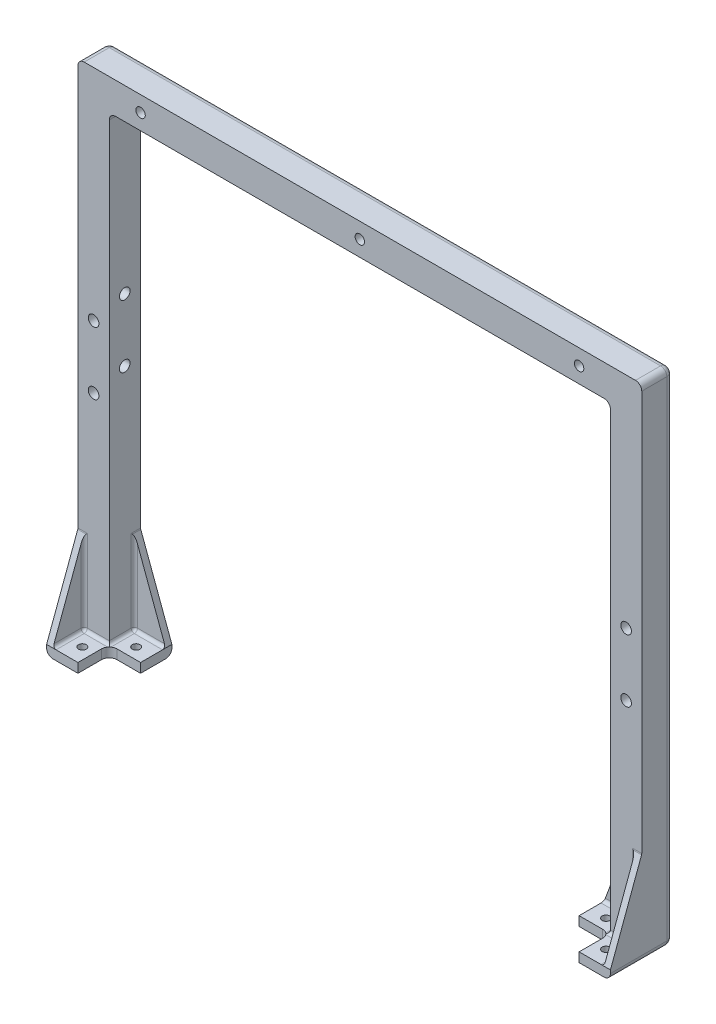
SolidWorks part; units mm, degrees
material "PLA"
ref_plane "Front Plane" through (0, 0, 0) normal (0, 0, 1) x (1, 0, 0)
ref_plane "Top Plane" through (0, 0, 0) normal (0, 1, 0) x (1, 0, 0)
ref_plane "Right Plane" through (0, 0, 0) normal (1, 0, 0) x (0, 0, -1)
sketch "Sketch1" plane through (0, 0, 0) normal (0, 0, 1) x (1, 0, 0)
  line L0 (0, 0) -> (39473.4142, 0) construction
  line L1 (0, 0) -> (0, 39473.4142) construction
  line L2 (-101.6, 0) -> (-101.6, 190.5)
  line L3 (-101.6, 190.5) -> (101.6, 190.5)
  line L4 (-101.6, 0) -> (-114.3, 0)
  line L5 (-114.3, 0) -> (-114.3, 203.2)
  line L6 (-114.3, 203.2) -> (114.3, 203.2)
  line L7 (114.3, 0) -> (114.3, 203.2)
  line L8 (101.6, 0) -> (114.3, 0)
  line L9 (101.6, 0) -> (101.6, 190.5)
  point P12 (0, 203.2)
  point P15 (0, 190.5)
  dimension "D1" = 190.5
  dimension "D2" = 203.2
  dimension "D3" = 203.2
  dimension "D4" = 228.6
extrude "Frame" add sketch "Sketch1" along normal blind 12.7
sketch "Sketch3" plane through (-114.3, 0, 0) normal (-1, 0, 0) x (0, 0, 1)
  line L0 (0, 0) -> (25.4, 0)
  line L1 (25.4, 0) -> (25.4, 3.81)
  line L2 (25.4, 3.81) -> (12.7, 38.1)
  line L3 (12.7, 38.1) -> (0, 38.1)
  line L4 (0, 203.2) -> (0, 0) construction
  line L5 (0, 38.1) -> (0, 0)
  line L6 (12.7, 203.2) -> (12.7, 0) construction
  dimension "D1" = 12.7
  dimension "D2" = 0
  dimension "D3" = 3.81
  dimension "D4" = 38.1
extrude "gusset_side" add sketch "Sketch3" against normal blind 2.54
mirror "gusset_mirror" about plane through (0, 0, 0) normal (1, 0, 0) of "gusset_side"
sketch "Sketch4" plane through (0, 0, 0) normal (0, -1, 0) x (-1, 0, 0)
  line L0 (101.6, 0) -> (101.6, -25.4)
  line L1 (101.6, -25.4) -> (114.3, -25.4)
  line L2 (114.3, -25.4) -> (114.3, 0) construction
  line L3 (114.3, -25.4) -> (114.3, 0)
  line L4 (114.3, 0) -> (101.6, 0)
  line L6 (111.76, -25.4) -> (114.3, -25.4) construction
extrude "bottom_mount_plate" add sketch "Sketch4" against normal up to vertex (3.81 mm away) up to point (-111.76, 3.81, 25.4)
mirror "Mirror2" about plane through (0, 0, 0) normal (1, 0, 0) of "bottom_mount_plate"
sketch "Sketch5" plane through (0, 0, 0) normal (0, 0, -1) x (-1, 0, 0)
  line L0 (-114.3, 0) -> (-88.9, 0)
  line L1 (-88.9, 0) -> (-88.9, 3.81)
  line L2 (-88.9, 3.81) -> (-101.6, 38.1)
  line L3 (-101.6, 38.1) -> (-114.3, 38.1)
  line L4 (-114.3, 0) -> (-114.3, 203.2) construction
  line L5 (-114.3, 38.1) -> (-114.3, 0)
  line L6 (-101.6, 190.5) -> (-101.6, 0) construction
  dimension "D1" = 3.81
  dimension "D2" = 0
  dimension "D3" = 38.1
  dimension "D4" = 12.7
extrude "gusset_front" add sketch "Sketch5" against normal blind 2.54
mirror "Mirror3" about plane through (0, 0, 0) normal (1, 0, 0) of "gusset_front"
sketch "Sketch6" plane through (0, 0, 0) normal (0, -1, 0) x (1, 0, 0)
  line L0 (114.3, 0) -> (88.9, 0)
  line L1 (88.9, 0) -> (88.9, 12.7)
  line L2 (88.9, 12.7) -> (114.3, 12.7)
  line L3 (114.3, 25.4) -> (114.3, 0) construction
  line L4 (114.3, 12.7) -> (114.3, 0)
  dimension "D1" = 12.7
extrude "bottom_mount_plate2" add sketch "Sketch6" against normal up to vertex (3.81 mm away) up to point (88.9, 3.81, 2.54)
mirror "Mirror4" about plane through (0, 0, 0) normal (1, 0, 0) of "bottom_mount_plate2"
fillet "Fillet1" radius 1.27 8 edges at (101.6, 38.1, 1.27) (-101.6, 20.955, 2.54) (-101.6, 38.1, 1.27) (101.6, 20.955, 2.54) (-113.03, 38.1, 12.7) (111.76, 20.955, 12.7) (113.03, 38.1, 12.7) (-111.76, 20.955, 12.7)
fillet "Fillet2" radius 3.175 2 edges at (101.6, 1.905, 12.7) (-101.6, 1.905, 12.7)
fillet "Fillet4" radius 1.27 12 edges at (106.045, 3.81, 12.7) (111.388, 3.81, 13.072) (101.6, 3.81, 8.255) (101.228, 3.81, 2.912) (-94.615, 3.81, 2.54) (-101.228, 3.81, 2.912) (-111.76, 3.81, 19.685) (-111.388, 3.81, 13.072) (111.76, 3.81, 19.685) (94.615, 3.81, 2.54) (-101.6, 3.81, 8.255) (-106.045, 3.81, 12.7)
sketch "Sketch7" plane through (0, 3.81, 0) normal (0, 1, 0) x (1, 0, 0)
  line L0 (-114.3, -25.4) -> (-114.3, 0) construction
  line L1 (-114.3, 0) -> (-88.9, 0) construction
  line L2 (-114.3, -12.7) -> (-114.3, 0) construction
  line L3 (114.3, 0) -> (-114.3, 0) construction
  line L12 (0, 0) -> (0, 50000) construction
  circle A0 centre (-106.172, -19.05) radius 1.5875
  circle A3 centre (-95.25, -8.128) radius 1.5875
  circle A4 centre (95.25, -8.128) radius 1.5875
  circle A5 centre (106.172, -19.05) radius 1.5875
  point P20 (0, 0)
  dimension "D3" = 3.175
  dimension "D5" = 3.175
  dimension "D2" = 8.128
  dimension "D4" = 19.05
  dimension "D6" = 19.05
  dimension "D7" = 8.128
extrude "Bottom-Mounting-Holes" cut sketch "Sketch7" against normal through all
sketch "Sketch8" plane through (0, 0, 12.7) normal (0, 0, 1) x (1, 0, 0)
  line L0 (0, 190.5) -> (0, 203.2) construction
  line L1 (-101.6, 190.5) -> (101.6, 190.5) construction
  line L2 (114.3, 203.2) -> (-114.3, 203.2) construction
  line L3 (-88.9, 196.85) -> (0, 196.85) construction
  circle A0 centre (0, 196.85) radius 1.905
  circle A1 centre (-88.9, 196.85) radius 1.905
  circle A2 centre (88.9, 196.85) radius 1.905
  dimension "D1" = 3.81
  dimension "D2" = 3.81
  dimension "D3" = 88.9
extrude "Top-MountingHoles" cut sketch "Sketch8" against normal blind 7.112
sketch "Sketch9" plane through (101.6, 0, 0) normal (-1, 0, 0) x (0, 0, 1)
  line L0 (6.35, 203.2) -> (6.5405, 0) construction
  line L1 (12.7, 203.2) -> (0, 203.2) construction
  circle A0 centre (6.4244, 123.825) radius 2.159
  circle A1 centre (6.4482, 98.425) radius 2.159
  dimension "D1" = 4.318
  dimension "D2" = 4.318
  dimension "D3" = 123.825
  dimension "D4" = 98.425
extrude "Brace-Mounting-Holes" cut sketch "Sketch9" against normal blind 7.112
mirror "Mirror5" about plane through (0, 0, 0) normal (1, 0, 0) of "Brace-Mounting-Holes"
sketch "Sketch10" plane through (0, 0, 12.7) normal (0, 0, 1) x (1, 0, 0)
  line L0 (0, 0) -> (0, 203.2) construction
  line L1 (114.3, 203.2) -> (-114.3, 203.2) construction
  line L2 (-101.6, 97.79) -> (-114.3, 97.79) construction
  line L3 (-101.6, 5.08) -> (-101.6, 190.5) construction
  line L4 (-114.3, 203.2) -> (-114.3, 38.3276) construction
  line L5 (-114.3, 101.6) -> (-101.6, 101.6) construction
  line L6 (-107.95, 114.3) -> (-107.95, 88.9) construction
  line L7 (107.95, 114.3) -> (107.95, 88.9) construction
  line L8 (114.3, 101.6) -> (101.6, 101.6) construction
  line L9 (101.6, 97.79) -> (114.3, 97.79) construction
  circle A0 centre (-107.95, 114.3) radius 2.159
  circle A1 centre (-107.95, 88.9) radius 2.159
  circle A2 centre (107.95, 88.9) radius 2.159
  circle A3 centre (107.95, 114.3) radius 2.159
  point P17 (-107.95, 101.6)
  point P18 (-107.95, 126.8387)
  point P30 (107.95, 101.6)
  dimension "D1" = 4.318
  dimension "D2" = 4.318
  dimension "D3" = 25.4
  dimension "D4" = 101.6
extrude "Cut-Extrude1" cut sketch "Sketch10" against normal blind 7.112
fillet "Fillet5" radius 2.54 8 edges at (114.3, 0, 12.7) (114.3, 203.2, 6.35) (-114.3, 0, 12.7) (-114.3, 203.2, 6.35) (-101.6, 0, 0) (-114.3, 101.6, 0) (114.3, 101.6, 0) (101.6, 0, 0)
fillet "Fillet6" radius 2.54 5 edges at (113.5561, 202.4561, 0.7439) (-113.5561, 202.4561, 0.7439) (0, 203.2, 0) (101.6, 190.5, 6.35) (-101.6, 190.5, 6.35)
sketch "Sketch11" plane through (0, 190.5, 0) normal (0, -1, 0) x (1, 0, 0)
  line L0 (0, 0) -> (0, 12.7) construction
  line L1 (-99.06, 12.7) -> (99.06, 12.7) construction
  line L2 (0, 6.35) -> (-12.7, 6.35) construction
  circle A0 centre (-12.7, 6.35) radius 2.159
  circle A1 centre (12.7, 6.35) radius 2.159
  dimension "D1" = 4.318
  dimension "D2" = 25.4
extrude "Cut-Extrude2" cut sketch "Sketch11" against normal blind 7.112
equation "\"D2@Sketch9\"=\"D1@Sketch9\""
